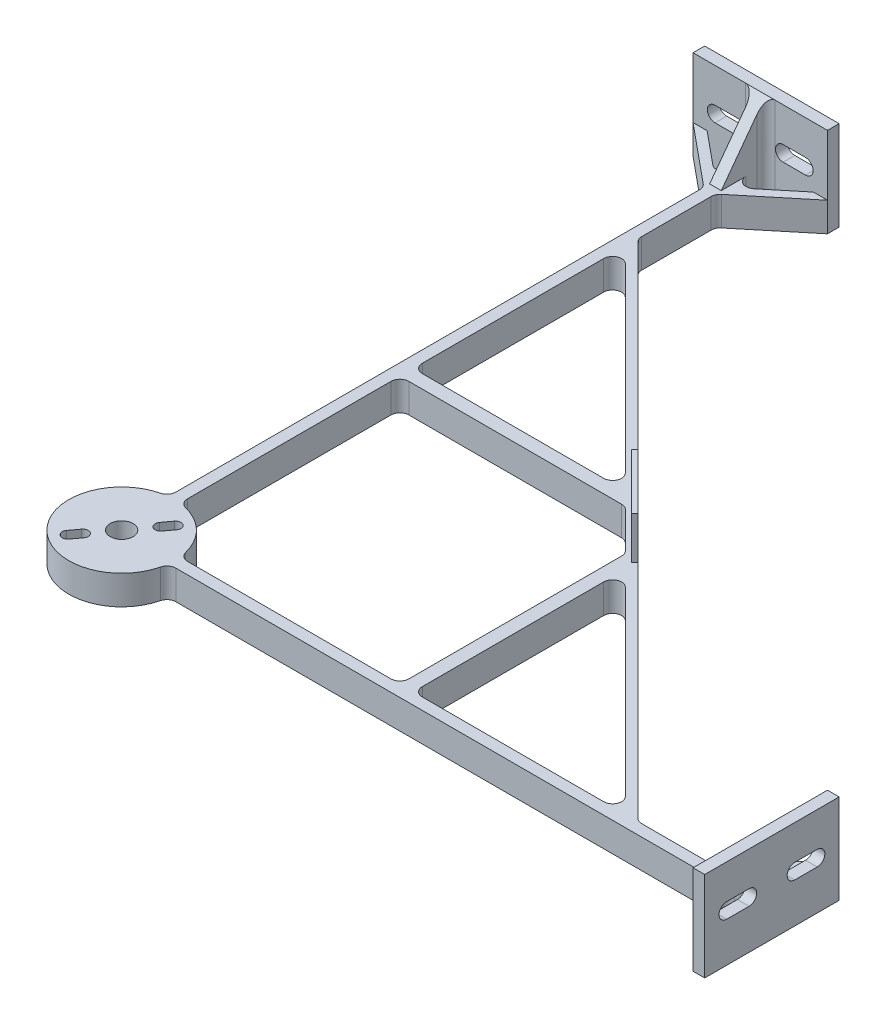
SolidWorks part; units mm, degrees
ref_plane "Front Plane" through (0, 0, 0) normal (0, 0, 1) x (1, 0, 0)
ref_plane "Top Plane" through (0, 0, 0) normal (0, 1, 0) x (1, 0, 0)
ref_plane "Right Plane" through (0, 0, 0) normal (1, 0, 0) x (0, 0, -1)
sketch "Sketch1" plane through (0, 0, 0) normal (0, 1, 0) x (1, 0, 0)
  line L0 (1.651, 14.8948) -> (1.651, 77.2021)
  line L1 (0, 0) -> (0, 189.2633) construction
  line L2 (-1.651, 14.8948) -> (-1.651, 180.975)
  line L3 (-1.651, 180.975) -> (1.651, 180.975)
  line L4 (-12.33, -16.663) -> (12.0176, 16.2408) construction
  line L5 (14.8948, -1.651) -> (180.975, -1.651)
  line L6 (4.6836, 6.3296) -> (6.4967, 8.7797) construction
  line L7 (3.4586, 7.2361) -> (5.2716, 9.6862)
  line L8 (180.975, -1.651) -> (180.975, 1.651)
  line L9 (14.8948, 1.651) -> (141.0789, 1.651)
  line L10 (5.9087, 5.4231) -> (7.7217, 7.8732)
  line L11 (0, 0) -> (16.238, -12.0155) construction
  line L12 (-4.6836, -6.3296) -> (-6.4967, -8.7797) construction
  line L13 (-5.9087, -5.4231) -> (-7.7217, -7.8732)
  line L14 (-3.4586, -7.2361) -> (-5.2716, -9.6862)
  line L15 (-1.651, 14.8948) -> (14.8948, -1.651) construction
  line L16 (1.651, 141.0789) -> (61.7178, 81.0121)
  line L17 (144.6711, 1.651) -> (1.651, 144.6711)
  line L18 (144.6711, 1.651) -> (166.629, 1.651)
  line L19 (141.0789, 1.651) -> (144.6711, 1.651) construction
  line L20 (1.651, 144.6711) -> (1.651, 180.975)
  line L21 (1.651, 81.0121) -> (61.7178, 81.0121)
  line L22 (1.651, 77.2021) -> (65.5278, 77.2021)
  line L23 (0, 0) -> (69.7604, 69.7604) construction
  line L24 (77.2021, 1.651) -> (77.2021, 65.5278)
  line L25 (81.0121, 1.651) -> (81.0121, 61.7178)
  line L26 (81.0121, 61.7178) -> (141.0789, 1.651)
  line L27 (65.5278, 77.2021) -> (77.2021, 65.5278)
  line L28 (1.651, 81.0121) -> (1.651, 141.0789)
  line L29 (169.921, 1.651) -> (180.975, 15.0573)
  line L30 (180.975, 15.0573) -> (180.975, 19.05)
  line L31 (180.975, 19.05) -> (166.629, 1.651)
  line L32 (166.4345, 0) -> (201.9953, 0) construction
  line L33 (180.975, -19.05) -> (166.629, -1.651)
  line L34 (180.975, -15.0573) -> (180.975, -19.05)
  line L35 (169.921, -1.651) -> (180.975, -15.0573)
  line L36 (169.921, 1.651) -> (180.975, 1.651)
  line L37 (166.629, 1.651) -> (169.921, 1.651) construction
  line L38 (-15.0573, 180.975) -> (-19.05, 180.975)
  line L39 (-19.05, 180.975) -> (-1.651, 166.629)
  line L40 (-1.651, 169.921) -> (-15.0573, 180.975)
  line L41 (1.651, 169.921) -> (15.0573, 180.975)
  line L42 (15.0573, 180.975) -> (19.05, 180.975)
  line L43 (19.05, 180.975) -> (1.651, 166.629)
  arc A0 (14.8948, 1.651) -> (1.651, 14.8948) centre (0, 0) ccw
  circle A1 centre (0, 0) radius 3.2385
  arc A2 (3.4586, 7.2361) -> (5.9087, 5.4231) centre (4.6836, 6.3296) ccw
  arc A3 (7.7217, 7.8732) -> (5.2716, 9.6862) centre (6.4967, 8.7797) ccw
  arc A4 (-5.9087, -5.4231) -> (-3.4586, -7.2361) centre (-4.6836, -6.3296) cw
  arc A5 (-5.2716, -9.6862) -> (-7.7217, -7.8732) centre (-6.4967, -8.7797) cw
  arc A6 (-1.651, 14.8948) -> (14.8948, -1.651) centre (0, 0) ccw
  point P14 (5.5901, 7.5546)
  point P25 (-5.5901, -7.5546)
  point P34 (142.875, 1.651)
  point P53 (168.275, 1.651)
  dimension "D3" = 29.972
  dimension "D1" = 6.477
  dimension "D6" = 1.524
  dimension "D7" = 3.048
  dimension "D2" = 36.5
  dimension "D4" = 3.302
  dimension "D5" = 3.302
  dimension "D8" = 7.874
  dimension "D9" = 2.54
  dimension "D10" = 38.1
  dimension "D11" = 3.81
  dimension "D12" = 16.51
  dimension "D13" = 38.1
  dimension "D14" = 12.7
  dimension "D15" = 2.54
  dimension "D16" = 180.975
  dimension "D17" = 180.975
extrude "Boss-Extrude1" add sketch "Sketch1" along normal blind 8.255 contours L2 A6 L5 L8 L36 L29 L30 L31 L18 L17 L20 L3 L14 A5 L13 A4 L9 A0 L0 L22 L27 L24 L25 L26 L21 L28 L16 A1 A3 L10 A2 L7 | L35 L5 L33 L34 | L2 L40 L38 L39 | L43 L42 L41 L20 region at (1.1203, 0, -90.7619) region at (-9.3955, 0, -174.5894) region at (174.5894, 0, 9.3955) region at (9.3955, 0, -174.5894)
sketch "Sketch3" plane through (0, 0, 0) normal (0, 1, 0) x (1, 0, 0)
  line L0 (0, 0) -> (128.7769, 128.7769) construction
  line L1 (180.975, 19.05) -> (184.277, 19.05)
  line L2 (180.975, 19.05) -> (180.975, -19.05)
  line L3 (180.975, -19.05) -> (184.277, -19.05)
  line L4 (184.277, 19.05) -> (184.277, -19.05)
  line L5 (19.05, 184.277) -> (-19.05, 184.277)
  line L6 (-19.05, 180.975) -> (-19.05, 184.277)
  line L7 (19.05, 180.975) -> (-19.05, 180.975)
  line L8 (19.05, 180.975) -> (19.05, 184.277)
  dimension "D1" = 3.302
extrude "Boss-Extrude3" add sketch "Sketch3" along normal blind 25.4
sketch "Sketch4" plane through (0, 8.255, 0) normal (0, 1, 0) x (1, 0, 0)
  line L0 (65.2584, 81.0637) -> (64.3604, 80.1656)
  line L1 (144.6711, 1.651) -> (1.651, 144.6711) construction
  line L2 (64.3604, 80.1656) -> (80.1656, 64.3604)
  line L3 (80.1656, 64.3604) -> (81.0637, 65.2584)
  line L4 (81.0637, 65.2584) -> (65.2584, 81.0637)
  line L5 (71.365, 71.365) -> (72.263, 72.263) construction
  line L6 (65.5278, 77.2021) -> (77.2021, 65.5278) construction
  dimension "D1" = 22.352
  dimension "D2" = 1.27
extrude "Boss-Extrude4" add sketch "Sketch4" along normal blind 11.938
sketch "Sketch5" plane through (184.277, 0, 0) normal (1, 0, 0) x (0, 0, -1)
  line L0 (-12.827, 13.4726) -> (-6.477, 13.4726) construction
  line L1 (-12.827, 15.6316) -> (-6.477, 15.6316)
  line L2 (-12.827, 11.3136) -> (-6.477, 11.3136)
  line L3 (0, 4.9298) -> (0, 30.0782) construction
  line L4 (12.827, 13.4726) -> (6.477, 13.4726) construction
  line L5 (12.827, 15.6316) -> (6.477, 15.6316)
  line L6 (12.827, 11.3136) -> (6.477, 11.3136)
  arc A0 (-12.827, 15.6316) -> (-12.827, 11.3136) centre (-12.827, 13.4726) ccw
  arc A1 (-6.477, 11.3136) -> (-6.477, 15.6316) centre (-6.477, 13.4726) ccw
  arc A2 (12.827, 15.6316) -> (12.827, 11.3136) centre (12.827, 13.4726) cw
  arc A3 (6.477, 11.3136) -> (6.477, 15.6316) centre (6.477, 13.4726) cw
  point P2 (-9.652, 13.4726)
  point P12 (9.652, 13.4726)
  dimension "D1" = 6.35
  dimension "D2" = 4.318
  dimension "D3" = 9.652
ref_plane "Plane1" through (0, 0, 0) normal (0.7071, 0, 0.7071) x (0.7071, 0, -0.7071)
extrude "Cut-Extrude1" cut sketch "Sketch5" against normal through all
mirror "Mirror1" about plane through (0, 0, 0) normal (0.7071, 0, 0.7071) of "Cut-Extrude1"
sketch "Sketch6" plane through (0, 0, 0) normal (0, 1, 0) x (1, 0, 0)
  line L0 (169.921, 1.651) -> (180.975, 1.651) construction
  line L1 (180.975, -1.651) -> (168.275, -1.651)
  line L2 (180.975, -1.651) -> (180.975, 1.651)
  line L3 (180.975, 1.651) -> (168.275, 1.651)
  line L4 (168.275, -1.651) -> (168.275, 1.651)
  dimension "D1" = 12.7
extrude "Boss-Extrude5" add sketch "Sketch6" along normal blind 25.4
sketch "Sketch7" plane through (0, 0, -1.651) normal (0, 0, -1) x (-1, 0, 0)
  line L0 (-180.975, 25.4) -> (-168.275, 8.255)
  line L1 (-168.275, 8.255) -> (-168.275, 25.4)
  line L2 (-168.275, 25.4) -> (-180.975, 25.4)
extrude "Cut-Extrude2" cut sketch "Sketch7" against normal blind 25.4
sketch "Sketch8" plane through (0, 0, 0) normal (0, 1, 0) x (1, 0, 0)
  line L0 (1.651, 169.921) -> (1.651, 180.975) construction
  line L1 (-1.651, 180.975) -> (1.651, 180.975)
  line L2 (-1.651, 180.975) -> (-1.651, 168.275)
  line L3 (-1.651, 168.275) -> (1.651, 168.275)
  line L4 (1.651, 180.975) -> (1.651, 168.275)
  dimension "D1" = 12.7
extrude "Boss-Extrude6" add sketch "Sketch8" along normal blind 25.4
sketch "Sketch9" plane through (1.651, 0, 0) normal (1, 0, 0) x (0, 0, -1)
  line L0 (180.975, 25.4) -> (168.275, 8.255)
  line L1 (168.275, 8.255) -> (168.275, 25.4)
  line L2 (168.275, 25.4) -> (180.975, 25.4)
extrude "Cut-Extrude3" cut sketch "Sketch9" against normal blind 25.4
fillet "Fillet1" radius 2.54 28 edges at (180.975, 12.7, 1.651) (-1.651, 12.7, -180.975) (141.0789, 4.1275, -1.651) (61.7178, 4.1275, -81.0121) (1.651, 4.1275, -141.0789) (81.0121, 4.1275, -61.7178) (14.8948, 4.1275, 1.651) (-1.651, 4.1275, -14.8948) (180.975, 12.7, -1.651) (77.2021, 4.1275, -1.651) (1.651, 12.7, -180.975) (1.651, 4.1275, -77.2021) (166.629, 4.1275, 1.651) (65.5278, 4.1275, -77.2021) (-1.651, 4.1275, -166.629) (77.2021, 4.1275, -65.5278) (1.651, 4.1275, -166.629) (1.651, 4.1275, -14.8948) (1.651, 4.1275, -144.6711) (1.651, 4.1275, -81.0121) (81.0121, 4.1275, -1.651) (166.629, 4.1275, -1.651) (14.8948, 4.1275, -1.651) (144.6711, 4.1275, -1.651) (1.651, 4.1275, -169.921) (-1.651, 4.1275, -169.921) (169.921, 4.1275, -1.651) (169.921, 4.1275, 1.651)
